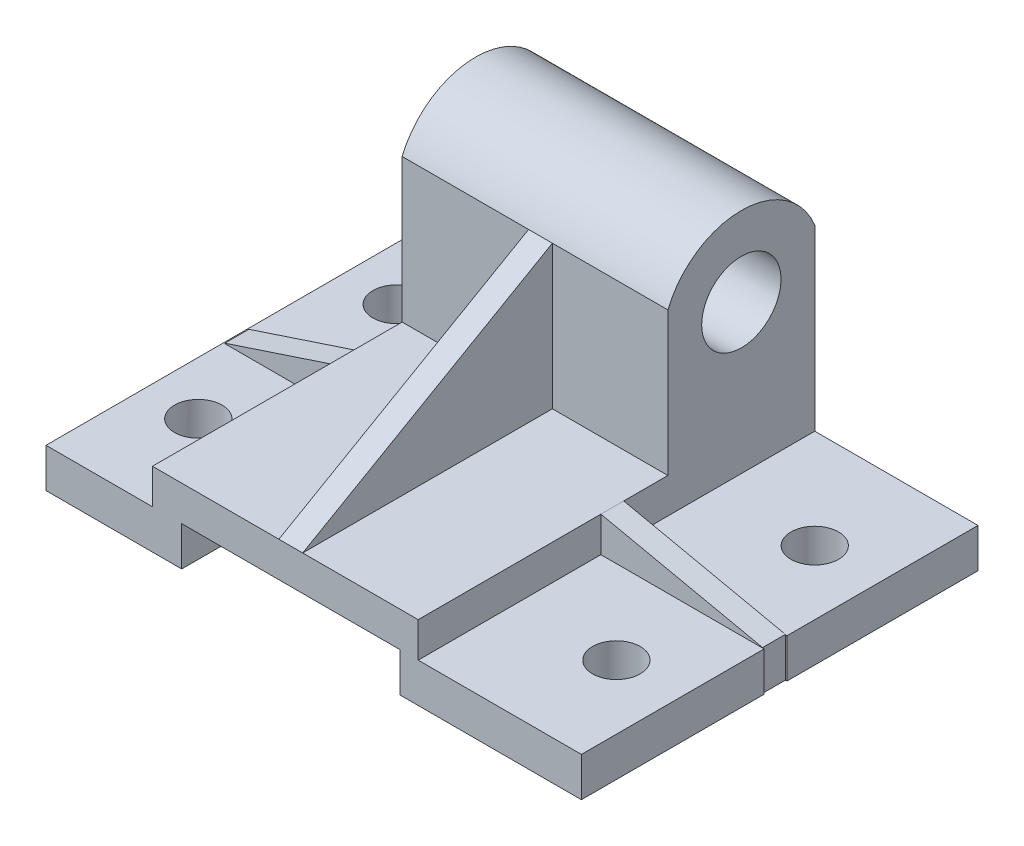
SolidWorks part; units mm, degrees
ref_plane "Front Plane" through (0, 0, 0) normal (0, 0, 1) x (1, 0, 0)
ref_plane "Top Plane" through (0, 0, 0) normal (0, 1, 0) x (1, 0, 0)
ref_plane "Right Plane" through (0, 0, 0) normal (1, 0, 0) x (0, 0, -1)
sketch "Sketch1" plane through (0, 0, 0) normal (0, 0, 1) x (1, 0, 0)
  line L0 (-61.7237, 0) -> (-27.5, 0)
  line L2 (-27.5, 0) -> (-27.5, 9.9022)
  line L3 (-27.5, 9.9022) -> (27.5, 9.9022)
  line L4 (27.5, 9.9022) -> (27.5, 0)
  line L5 (27.5, 0) -> (73.2763, 0)
  line L6 (-61.7237, 0) -> (-61.7237, 9.9022)
  line L9 (73.2763, 9.9022) -> (73.2763, 0)
  line L10 (-61.7237, 9.9022) -> (-34.8805, 9.9022)
  line L11 (-34.8805, 9.9022) -> (-34.8805, 18.75)
  line L12 (-34.8805, 18.75) -> (31.6683, 18.75)
  line L13 (31.6683, 18.75) -> (31.6683, 9.9022)
  line L14 (31.6683, 9.9022) -> (73.2763, 9.9022)
  point P6 (0, 0)
  dimension "D1" = 135
  dimension "D2" = 55
extrude "Boss-Extrude1" add sketch "Sketch1" against normal blind 100
sketch "Sketch2" plane through (-34.8805, 0, 0) normal (-1, 0, 0) x (0, 0, 1)
  line L0 (-100, 9.9022) -> (-100, 54.9088)
  line L1 (-62.9612, 54.9088) -> (-62.9612, 18.75)
  line L2 (-100, 18.75) -> (0, 18.75) construction
  line L3 (-62.9612, 18.75) -> (0, 18.75)
  line L4 (0, 18.75) -> (0, 9.9022)
  line L5 (0, 9.9022) -> (-100, 9.9022)
  arc A0 (-100, 54.9088) -> (-62.9612, 54.9088) centre (-81.4806, 47.3569) cw
  circle A1 centre (-81.4806, 47.3569) radius 10
  dimension "D1" = 20
  dimension "D2" = 20
extrude "Boss-Extrude2" add sketch "Sketch2" against normal blind 67
sketch "Sketch3" plane through (0, 9.9022, 0) normal (0, 1, 0) x (1, 0, 0)
  line L0 (-48.3021, 100) -> (-48.3021, 0) construction
  line L1 (-34.8805, 100) -> (-61.7237, 100) construction
  line L2 (-34.8805, 0) -> (-61.7237, 0) construction
  line L3 (-61.7237, 100) -> (-61.7237, 75.0046) construction
  line L4 (-61.7237, 100) -> (-61.7237, 0) construction
  line L5 (-61.7237, 0) -> (-61.7237, 24.9835) construction
  line L6 (-61.7237, 50) -> (73.2763, 50) construction
  line L7 (73.2763, 100) -> (73.2763, 0) construction
  circle A0 centre (-48.3021, 24.9835) radius 6
  circle A1 centre (-48.3021, 75.0046) radius 6
  dimension "D1" = 12
  dimension "D2" = 12
extrude "Cut-Extrude1" cut sketch "Sketch3" against normal blind 67
sketch "Sketch4" plane through (0, 0, 0) normal (0, 1, 0) x (1, 0, 0)
  line L0 (-48.3021, 75.0046) -> (73.2763, 75.0046) construction
  line L1 (73.2763, 100) -> (73.2763, 0) construction
  line L2 (-48.3021, 24.9835) -> (73.2763, 24.9835) construction
  circle A0 centre (57.109, 75.0046) radius 6
  circle A1 centre (57.109, 24.9835) radius 6
  dimension "D1" = 12
  dimension "D2" = 12
extrude "Cut-Extrude2" cut sketch "Sketch4" along normal blind 67 and the other way blind 67
sketch "Sketch5" plane through (0, 0, 0) normal (1, 0, 0) x (0, 0, -1)
  line L0 (62.9612, 54.9088) -> (0, 18.75)
  line L1 (0, 18.75) -> (62.9612, 18.75)
  line L2 (62.9612, 18.75) -> (62.9612, 54.9088)
extrude "Boss-Extrude3" add sketch "Sketch5" along normal mid plane 6
ref_plane "Plane1" through (0, 10, 0) normal (0, 1, 0) x (1, 0, 0)
ref_plane "Plane2" through (-30, 0, 0) normal (1, 0, 0) x (0, 0, -1)
sketch "Sketch9" plane through (-34.8805, 0, 0) normal (-1, 0, 0) x (0, 0, 1)
  line L0 (-50.8076, 18.75) -> (-50.8076, 9.9022)
  line L1 (-62.9612, 18.75) -> (0, 18.75) construction
  line L2 (-100, 9.9022) -> (0, 9.9022) construction
  line L3 (-50.8076, 18.75) -> (-44.7399, 18.75)
  line L4 (-44.7399, 18.75) -> (-44.7399, 9.9022)
  line L5 (-44.7399, 9.9022) -> (-50.8076, 9.9022)
extrude "Boss-Extrude4" add sketch "Sketch9" along normal blind 26.5
sketch "Sketch10" plane through (0, 0, -44.7399) normal (0, 0, 1) x (1, 0, 0)
  line L0 (-34.8805, 18.75) -> (-61.3805, 10)
  line L1 (55, 10) -> (-55, 10) construction
  line L2 (-61.3805, 9.9022) -> (-61.3805, 18.75) construction
  line L3 (-61.3805, 10) -> (-61.3805, 18.75)
  line L4 (-61.3805, 18.75) -> (-34.8805, 18.75)
extrude "Cut-Extrude3" cut sketch "Sketch10" against normal blind 26.5
sketch "Sketch11" plane through (32.1195, 0, 0) normal (1, 0, 0) x (0, 0, -1)
  line L0 (46.0681, 18.75) -> (51.827, 18.75)
  line L1 (0, 18.75) -> (62.9612, 18.75) construction
  line L2 (51.827, 18.75) -> (51.827, 9.9022)
  line L3 (100, 9.9022) -> (0, 9.9022) construction
  line L4 (51.827, 9.9022) -> (46.0681, 9.9022)
  line L5 (46.0681, 9.9022) -> (46.0681, 18.75)
extrude "Boss-Extrude5" add sketch "Sketch11" along normal blind 42
sketch "Sketch12" plane through (0, 0, -51.827) normal (0, 0, -1) x (-1, 0, 0)
  line L0 (-32.1195, 18.75) -> (-72.8842, 10)
  line L1 (55, 10) -> (-55, 10) construction
  line L2 (-72.8842, 10) -> (-74.9758, 10)
  line L3 (-74.9758, 10) -> (-74.1195, 18.75)
  line L4 (-74.1195, 18.75) -> (-32.1195, 18.75)
extrude "Cut-Extrude4" cut sketch "Sketch12" against normal blind 42
sketch "Sketch13" plane through (0, 10, 0) normal (0, 1, 0) x (1, 0, 0)
  line L0 (72.8842, 51.827) -> (74.1195, 51.827)
  line L5 (74.1195, 51.827) -> (74.1195, 46.0681)
  line L6 (74.1195, 46.0681) -> (72.8842, 46.0681)
  line L7 (72.8842, 46.0681) -> (72.8842, 51.827)
extrude "Cut-Extrude6" cut sketch "Sketch13" against normal blind 42
